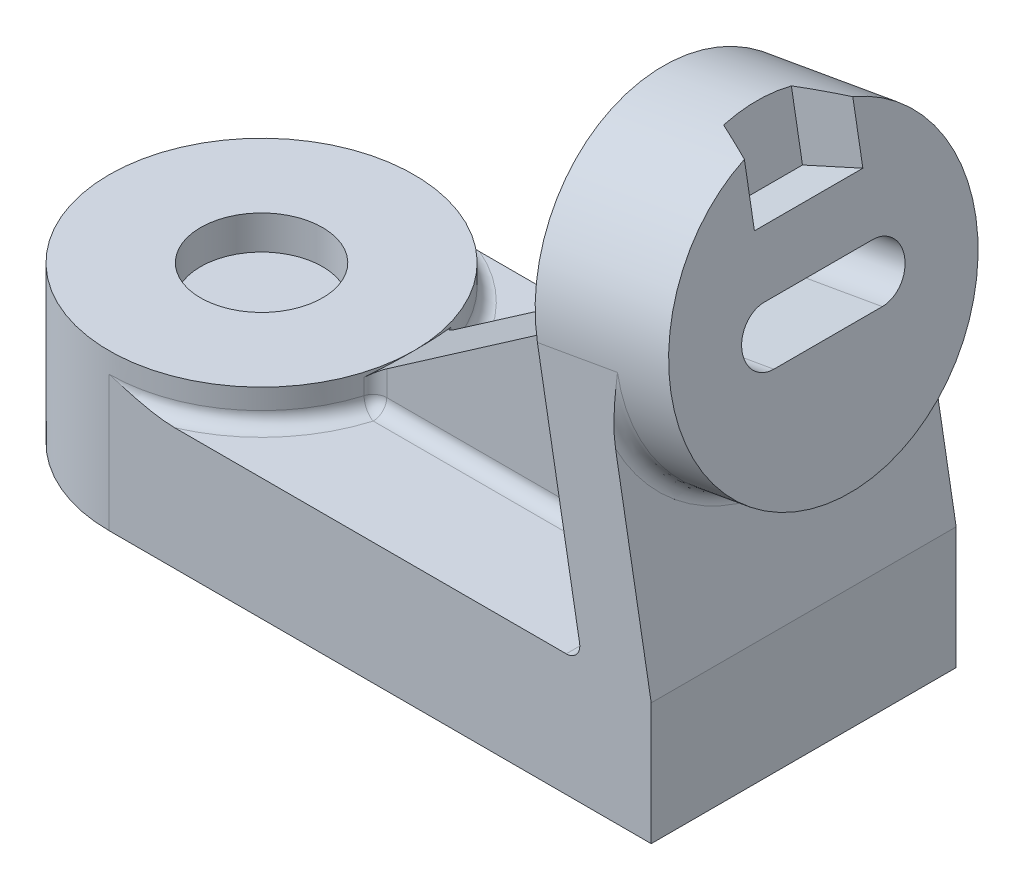
SolidWorks part; units mm, degrees
material "AISI 1035 Steel (SS)"
ref_plane "Front Plane" through (0, 0, 0) normal (0, 0, 1) x (1, 0, 0)
ref_plane "Top Plane" through (0, 0, 0) normal (0, 1, 0) x (1, 0, 0)
ref_plane "Right Plane" through (0, 0, 0) normal (1, 0, 0) x (0, 0, -1)
sketch "Sketch1" plane through (0, 0, 0) normal (0, 0, 1) x (1, 0, 0)
  line L0 (0, 0) -> (102.5, 0)
  line L1 (102.5, 0) -> (102.5, 18)
  line L2 (102.5, 18) -> (91.647, 79.5505)
  line L3 (91.647, 79.5505) -> (81.7989, 77.814)
  line L4 (81.7989, 77.814) -> (92.3457, 18)
  line L5 (92.3457, 18) -> (0, 18)
  line L6 (0, 18) -> (0, 0)
  dimension "D2" = 18
  dimension "D3" = 10
  dimension "D4" = 102.5
  dimension "D1" = 62.5
  dimension "D5" = 80
extrude "Boss-Extrude1" add sketch "Sketch1" along normal mid plane 45
fillet "Fillet1" 2 edges at (86.723, 78.6822, 22.5) (86.723, 78.6822, -22.5) type full round first side face at (67.2559, 30.1949, 22.5) second side face at (67.2559, 30.1949, -22.5) middle face at (86.723, 78.6822, 0)
fillet "Fillet2" 2 edges at (0, 9, -22.5) (0, 9, 22.5) type full round first side face at (68.3723, 23.864, -22.5) second side face at (68.3723, 23.864, 22.5) middle face at (0, 9, 0)
sketch "Sketch2" plane through (0, 18, 0) normal (0, 1, 0) x (1, 0, 0)
  circle A0 centre (22.5, 0) radius 22.5
  arc A1 (22.5, 22.5) -> (22.5, -22.5) centre (22.5, 0) ccw construction
  circle A2 centre (22.5, 0) radius 9
  dimension "D1" = 18
extrude "Boss-Extrude2" add sketch "Sketch2" along normal blind 5
sketch "Sketch3" plane through (102.4874, 18.0713, 0) normal (0.9848, 0.1736, 0) x (0, 0, -1)
  circle A0 centre (0, 39.9276) radius 22.5
  arc A1 (22.5, 39.9276) -> (-22.5, 39.9276) centre (0, 39.9276) ccw construction
extrude "Boss-Extrude3" add sketch "Sketch3" along normal blind 10
sketch "Sketch4" plane through (112.3355, 19.8078, 0) normal (0.9848, 0.1736, 0) x (0, 0, -1)
  line L0 (-8, 39.9276) -> (8, 39.9276) construction
  line L1 (-8, 43.9276) -> (8, 43.9276)
  line L2 (-8, 35.9276) -> (8, 35.9276)
  line L3 (-22.5, 39.9276) -> (22.5, 39.9276) construction
  arc A0 (-8, 43.9276) -> (-8, 35.9276) centre (-8, 39.9276) ccw
  arc A1 (8, 35.9276) -> (8, 43.9276) centre (8, 39.9276) ccw
  circle A3 centre (0, 39.9276) radius 22.5 construction
  point P2 (0, 39.9276)
  dimension "D2" = 4
  dimension "D1" = 16
extrude "Cut-Extrude1" cut sketch "Sketch4" against normal blind 30
sketch "Sketch5" plane through (0, 0, 0) normal (0, 0, 1) x (1, 0, 0)
  line L0 (86.4006, 51.7166) -> (45, 23)
  line L1 (85.0114, 59.5951) -> (86.4006, 51.7166) construction
  line L3 (86.4006, 51.7166) -> (106.0967, 55.1896) construction
  line L4 (45, 23) -> (0, 23) construction
  line L5 (45, 18) -> (45, 23) construction
rib "Rib1" sketch "Sketch5" sketch "Sketch5" thickness 10 extrusion direction parallel to sketch draft on no parameters "D1"=10
ref_plane "Plane1" through (-10.8404, 61.4792, 0) normal (-0.1736, 0.9848, 0) x (0.9848, 0.1736, 0)
sketch "Sketch8" plane through (-10.8404, 61.4792, 0) normal (-0.1736, 0.9848, 0) x (0.9848, 0.1736, 0)
  line L1 (108.0685, -5) -> (114.0685, -8)
  line L2 (114.0685, 8) -> (114.0685, -8) construction
  line L3 (114.0685, -8) -> (114.0685, 8)
  line L4 (114.0685, 8) -> (108.0685, 5)
  line L5 (108.0685, 5) -> (108.0685, -5)
  line L6 (114.0685, -22.5) -> (114.0685, 22.5) construction
  line L7 (114.0685, 8) -> (114.0685, 12) construction
  line L8 (94.0685, -5) -> (94.0685, 5) construction
  point P13 (94.0685, 0)
  point P14 (108.0685, 0)
  dimension "D1" = 10
  dimension "D2" = 6
  dimension "D3" = 16
extrude "Cut-Extrude2" cut sketch "Sketch8" against normal blind 10
fillet "Fillet3" radius 2 11 edges at (99.4612, 35.2341, 0) (44.4374, 20.3049, 5) (44.4374, 20.3049, -5) (36.5312, 18, -17.5891) (36.5312, 18, 17.5891) (92.3457, 18, 13.75) (89.3732, 34.8583, 5) (68.3916, 18, 5) (89.3732, 34.8583, -5) (68.3916, 18, -5) (92.3457, 18, -13.75)
equation "\"A\"= 80"
equation "\"B\"= 45"
equation "\"C\"= 18"
equation "\"D2@Sketch1\"=\"C\""
equation "\"D4@Sketch1\"=\"A\"+(\"B\"/2)"
equation "\"D1@Boss-Extrude1\"=\"B\""
equation "\"D1@Boss-Extrude2\"=23-\"C\""
equation "\"D1@Sketch1\"=\"B\"/2+40"
